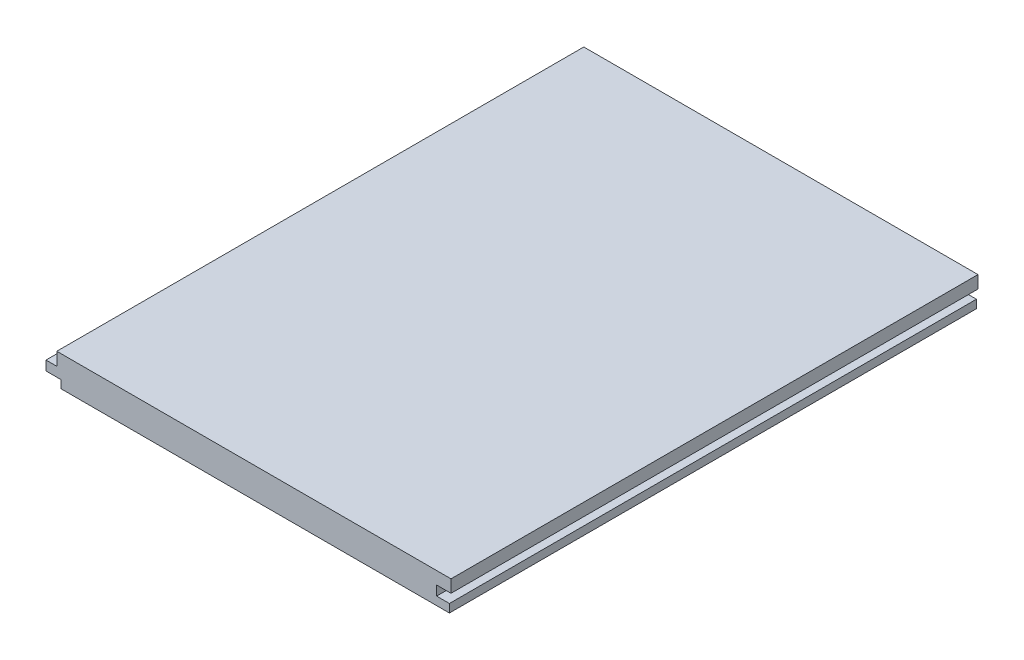
SolidWorks part; units mm, degrees
ref_plane "Front Plane" through (0, 0, 0) normal (0, 0, 1) x (1, 0, 0)
ref_plane "Top Plane" through (0, 0, 0) normal (0, 1, 0) x (1, 0, 0)
ref_plane "Right Plane" through (0, 0, 0) normal (1, 0, 0) x (0, 0, -1)
sketch "Sketch1" plane through (0, 0, 0) normal (0, 0, 1) x (1, 0, 0)
  line L0 (-94.996, 1.0541) -> (-100.203, 1.0541)
  line L1 (-94.996, 7.3279) -> (94.996, 7.3279)
  line L2 (-94.996, 7.3279) -> (-94.996, -7.3279)
  line L3 (-94.996, -7.3279) -> (94.996, -7.3279)
  line L4 (94.996, 7.3279) -> (94.996, -7.3279)
  line L5 (-94.996, 7.3279) -> (94.996, -7.3279) construction
  line L6 (-94.996, -7.3279) -> (94.996, 7.3279) construction
  line L7 (-100.203, 1.0541) -> (-100.203, -3.5179)
  line L8 (-100.203, -3.5179) -> (-92.964, -3.5179)
  line L9 (-92.964, -3.5179) -> (-92.964, -7.3279)
  line L10 (94.996, 1.2827) -> (88.0745, 1.2827)
  line L11 (88.0745, 1.2827) -> (88.0745, -3.3401)
  line L12 (88.0745, -3.3401) -> (94.234, -3.3401)
  line L13 (94.234, -3.3401) -> (94.234, -7.3279)
  dimension "D1" = 189.992
  dimension "D2" = 14.6558
  dimension "D3" = 6.2738
  dimension "D4" = 5.207
  dimension "D5" = 4.572
  dimension "D6" = 7.239
  dimension "D7" = 6.0452
  dimension "D8" = 4.6228
  dimension "D9" = 0.762
  dimension "D10" = 6.9215
extrude "Boss-Extrude1" add sketch "Sketch1" along normal mid plane 254 contours L13 L12 L11 L10 L4 L1 L2 L8 L9 L3 | L7 L8 L2 L0 region at (-97.5995, -1.2319, 0) region at (-0.9077, 0.0332, 0)
sketch "Sketch2" plane through (0, 0, 0) normal (0, 0, 1) x (1, 0, 0)
  line L0 (-92.964, -7.3279) -> (94.234, -7.3279) construction
  line L1 (-92.964, -7.3279) -> (94.234, -7.3279)
  point P2 (0.635, -7.3279)
